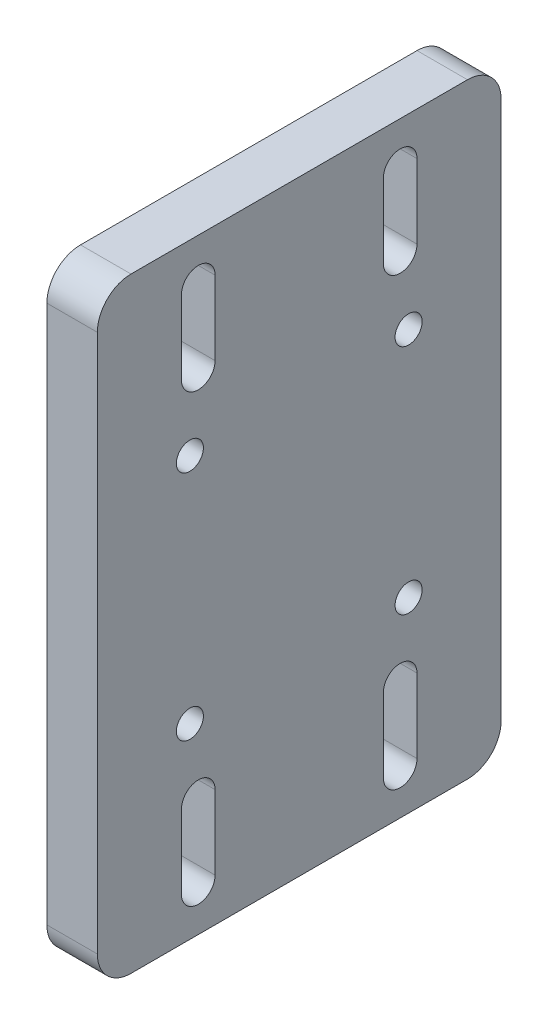
SolidWorks part; units mm, degrees
ref_plane "Front Plane" through (0, 0, 0) normal (0, 0, 1) x (1, 0, 0)
ref_plane "Top Plane" through (0, 0, 0) normal (0, 1, 0) x (1, 0, 0)
ref_plane "Right Plane" through (0, 0, 0) normal (1, 0, 0) x (0, 0, -1)
sketch "Sketch1" plane through (0, 0, 0) normal (1, 0, 0) x (0, 0, -1)
  line L1 (-38.1, -57.15) -> (38.1, -57.15)
  line L2 (-38.1, -57.15) -> (-38.1, 57.15)
  line L3 (-38.1, 57.15) -> (38.1, 57.15)
  line L4 (38.1, -57.15) -> (38.1, 57.15)
  line L5 (-38.1, -57.15) -> (38.1, 57.15) construction
  line L6 (-38.1, 57.15) -> (38.1, -57.15) construction
  point P0 (0, 0)
  point P5 (0, 0)
  dimension "D1" = 76.2
  dimension "D2" = 114.3
extrude "Boss-Extrude1" add sketch "Sketch1" along normal blind 9.525
hole_wizard "1/4-20 Tapped Hole1" positions "Sketch2" profile "Sketch3" tap size "1/4-20" standard "ANSI Inch" end condition through all
sketch "Sketch2" plane through (9.525, 0, 0) normal (1, 0, 0) x (0, 0, -1)
  line L1 (-20.6375, -21.9075) -> (20.6375, -21.9075) construction
  line L2 (-20.6375, -21.9075) -> (-20.6375, 21.9075) construction
  line L3 (-20.6375, 21.9075) -> (20.6375, 21.9075) construction
  line L4 (20.6375, -21.9075) -> (20.6375, 21.9075) construction
  line L5 (-20.6375, -21.9075) -> (20.6375, 21.9075) construction
  line L6 (-20.6375, 21.9075) -> (20.6375, -21.9075) construction
  point P0 (-20.6375, 21.9075)
  point P58 (20.6375, 21.9075)
  point P61 (20.6375, -21.9075)
  point P64 (-20.6375, -21.9075)
  dimension "D1" = 43.815
  dimension "D2" = 41.275
cosmetic thread "Hole Thread1" parameters "D2"=6.35
cosmetic thread "Hole Thread2" parameters "D2"=6.35
cosmetic thread "Hole Thread3" parameters "D2"=6.35
cosmetic thread "Hole Thread4" parameters "D2"=6.35
sketch "Sketch3" plane through (9.525, 21.9075, 20.6375) normal (0, 1, 0) x (0, 0, -1)
  line L0 (0, 0) -> (0, 9.525)
  line L1 (0, 9.525) -> (2.5527, 9.525)
  line L2 (2.5527, 9.525) -> (2.5527, 0)
  line L5 (2.5527, 0) -> (0, 0)
  line L11 (0, -6.35) -> (0, 107.95) construction
  dimension "Thru Tap Drill Dia." = 5.1054
  dimension "Thru Tap Drill Depth" = 9.525
sketch "Sketch4" plane through (9.525, 0, 0) normal (1, 0, 0) x (0, 0, -1)
  line L5 (19.05, 29.972) -> (19.05, 57.15) construction
  line L6 (38.1, 57.15) -> (-38.1, 57.15) construction
  line L7 (0, -57.15) -> (0, 57.15) construction
  line L8 (-29.972, 29.972) -> (29.972, 29.972) construction
  line L9 (-29.972, 29.972) -> (-29.972, -29.972) construction
  line L10 (-29.972, -29.972) -> (29.972, -29.972) construction
  line L11 (29.972, 29.972) -> (29.972, -29.972) construction
  line L12 (-29.972, 29.972) -> (29.972, -29.972) construction
  line L13 (-29.972, -29.972) -> (29.972, 29.972) construction
  line L14 (-38.1, -57.15) -> (38.1, -57.15) construction
  line L15 (-38.1, 0) -> (38.1, 0) construction
  line L16 (15.875, 49.022) -> (22.225, 49.022) construction
  line L17 (15.875, 49.022) -> (15.875, 35.052)
  line L18 (15.875, 35.052) -> (22.225, 35.052) construction
  line L19 (22.225, 49.022) -> (22.225, 35.052)
  line L20 (15.875, 49.022) -> (22.225, 35.052) construction
  line L21 (15.875, 35.052) -> (22.225, 49.022) construction
  line L22 (-38.1, 57.15) -> (-38.1, -57.15) construction
  line L23 (38.1, -57.15) -> (38.1, 57.15) construction
  line L24 (-15.875, 35.052) -> (-22.225, 49.022) construction
  line L25 (-15.875, 49.022) -> (-22.225, 35.052) construction
  line L26 (-15.875, 35.052) -> (-22.225, 35.052) construction
  line L27 (-15.875, 49.022) -> (-22.225, 49.022) construction
  line L28 (-22.225, 49.022) -> (-22.225, 35.052)
  line L29 (-15.875, 49.022) -> (-15.875, 35.052)
  line L30 (-15.875, -49.022) -> (-22.225, -49.022) construction
  line L31 (-15.875, -35.052) -> (-22.225, -35.052) construction
  line L32 (-15.875, -49.022) -> (-22.225, -35.052) construction
  line L33 (-15.875, -35.052) -> (-22.225, -49.022) construction
  line L34 (15.875, -35.052) -> (22.225, -49.022) construction
  line L35 (15.875, -49.022) -> (22.225, -35.052) construction
  line L36 (15.875, -35.052) -> (22.225, -35.052) construction
  line L37 (15.875, -49.022) -> (22.225, -49.022) construction
  line L38 (-15.875, -49.022) -> (-15.875, -35.052)
  line L39 (-22.225, -49.022) -> (-22.225, -35.052)
  line L40 (22.225, -49.022) -> (22.225, -35.052)
  line L41 (15.875, -49.022) -> (15.875, -35.052)
  line L42 (11.0908, 31.877) -> (29.972, 31.877) construction
  arc A0 (15.875, 49.022) -> (22.225, 49.022) centre (19.05, 49.022) cw
  arc A1 (22.225, 35.052) -> (15.875, 35.052) centre (19.05, 35.052) cw
  arc A2 (-22.225, 35.052) -> (-15.875, 35.052) centre (-19.05, 35.052) ccw
  arc A3 (-15.875, 49.022) -> (-22.225, 49.022) centre (-19.05, 49.022) ccw
  arc A4 (-15.875, -49.022) -> (-22.225, -49.022) centre (-19.05, -49.022) cw
  arc A5 (-22.225, -35.052) -> (-15.875, -35.052) centre (-19.05, -35.052) cw
  arc A6 (22.225, -35.052) -> (15.875, -35.052) centre (19.05, -35.052) ccw
  arc A7 (15.875, -49.022) -> (22.225, -49.022) centre (19.05, -49.022) ccw
  point P7 (0, 0)
  point P13 (19.05, 42.037)
  point P33 (-19.05, 42.037)
  point P46 (-19.05, -42.037)
  point P47 (19.05, -42.037)
  dimension "D4" = 19.05
  dimension "D1" = 13.97
  dimension "D2" = 59.944
  dimension "D3" = 6.35
  dimension "D5" = 1.905
extrude "Cut-Extrude1" cut sketch "Sketch4" against normal through all
ref_axis "Axis1" through (0, 0, 0) along (1, 0, 0)
fillet "Fillet1" radius 6.35 4 edges at (4.7625, -57.15, 38.1) (4.7625, -57.15, -38.1) (4.7625, 57.15, -38.1) (4.7625, 57.15, 38.1)
